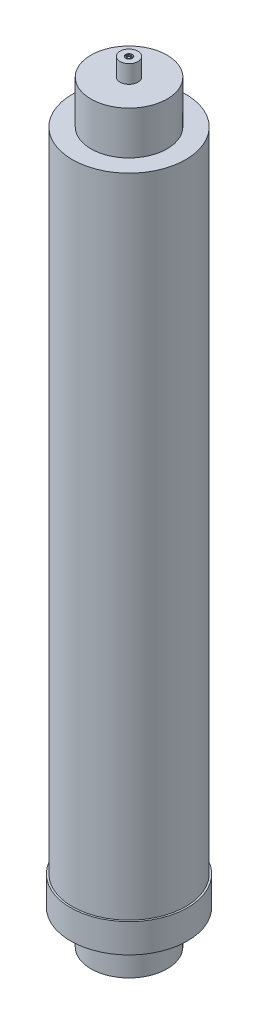
SolidWorks part; units mm, degrees
ref_plane "Front Plane" through (0, 0, 0) normal (0, 0, 1) x (1, 0, 0)
ref_plane "Top Plane" through (0, 0, 0) normal (0, 1, 0) x (1, 0, 0)
ref_plane "Right Plane" through (0, 0, 0) normal (1, 0, 0) x (0, 0, -1)
sketch "Sketch1" plane through (0, 0, 0) normal (0, 1, 0) x (1, 0, 0)
  circle A0 centre (0, 0) radius 53.975
  dimension "D1" = 107.95
extrude "Boss-Extrude1" add sketch "Sketch1" along normal blind 48.7426
sketch "Sketch2" plane through (0, 48.7426, 0) normal (0, 1, 0) x (1, 0, 0)
  circle A0 centre (0, 0) radius 82.931
  dimension "D1" = 165.862
extrude "Boss-Extrude2" add sketch "Sketch2" along normal blind 40.9194
sketch "Sketch3" plane through (0, 89.662, 0) normal (0, 1, 0) x (1, 0, 0)
  circle A0 centre (0, 0) radius 80.391
  dimension "D1" = 160.782
extrude "Boss-Extrude3" add sketch "Sketch3" along normal blind 917.194
sketch "Sketch4" plane through (0, 1006.856, 0) normal (0, 1, 0) x (1, 0, 0)
  circle A0 centre (0, 0) radius 53.975
  dimension "D1" = 107.95
extrude "Boss-Extrude4" add sketch "Sketch4" along normal blind 61.214
sketch "Sketch5" plane through (0, 1068.07, 0) normal (0, 1, 0) x (1, 0, 0)
  circle A0 centre (0, 0) radius 12.7
  dimension "D1" = 25.4
extrude "Boss-Extrude5" add sketch "Sketch5" along normal blind 25.4
sketch "Sketch6" plane through (0, 1093.47, 0) normal (0, 1, 0) x (1, 0, 0)
  circle A0 centre (0, 0) radius 4.7625
  dimension "D1" = 9.525
extrude "Cut-Extrude1" cut sketch "Sketch6" against normal blind 25.4
thread "Thread1" pitch 1.5875 method extrude profile "Thread Profile1" start angle 0, offset 0, length 25.4, pitch 1.5875, diameter 9.525
ref_plane "Plane1" through (-4.7625, 1093.47, 0) normal (0, 0, 1) x (-1, 0, 0)
sketch "Thread Profile1" plane through (-4.7625, 1093.47, 0) normal (0, 0, 1) x (-1, 0, 0)
  line L0 (0, 0) -> (0, 1.5875) construction
  line L11 (0, 0) -> (0, 1.3891)
  line L12 (0, 1.3891) -> (-0.8593, 0.893)
  line L13 (-0.8593, 0.893) -> (-0.8593, 0.4961)
  line L15 (-0.8593, 0.4961) -> (0, 0)
  line L17 (-0.8593, 0.6945) -> (0, 0.6945) construction
  point P2 (0, 0)
  dimension "Pitch" = 1.5875
  dimension "Profile_Angle" = 60
  dimension "Profile_Land" = 0.3969
  dimension "Profile_Height" = 0.8593
